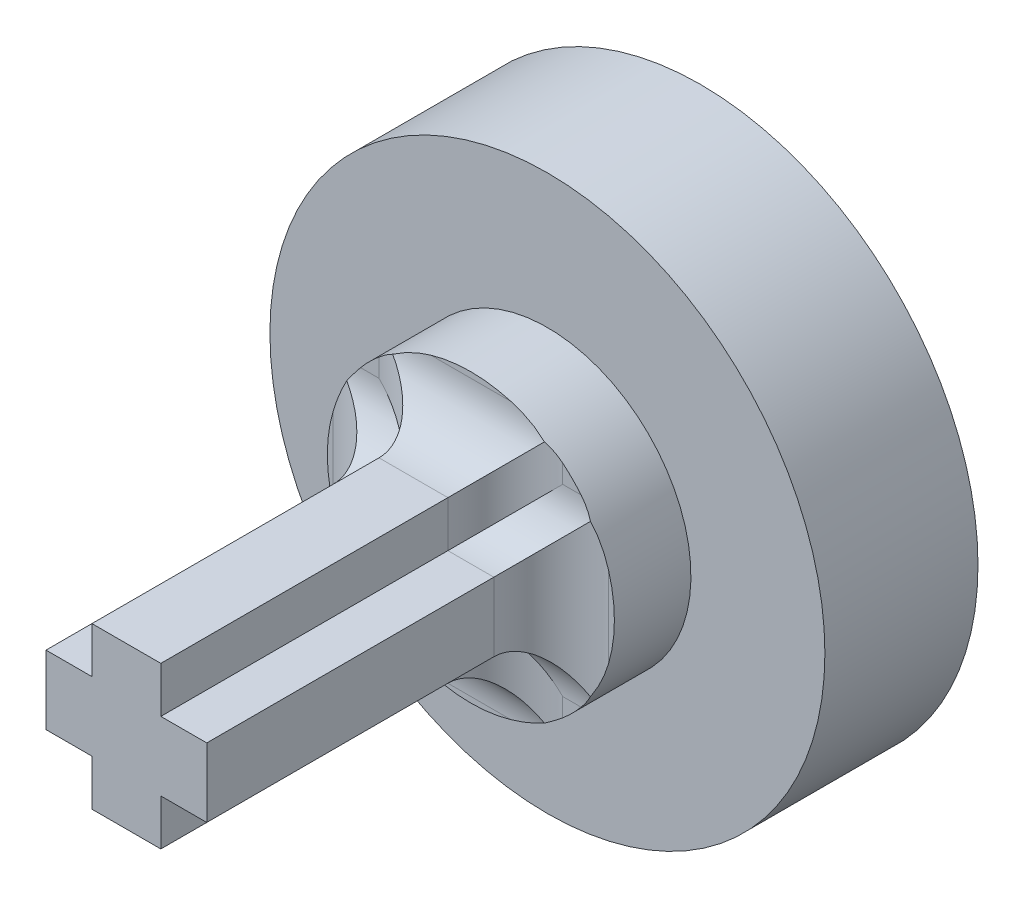
SolidWorks part; units mm, degrees
ref_plane "前视基准面" through (0, 0, 0) normal (0, 0, 1) x (1, 0, 0)
ref_plane "上视基准面" through (0, 0, 0) normal (0, 1, 0) x (1, 0, 0)
ref_plane "右视基准面" through (0, 0, 0) normal (1, 0, 0) x (0, 0, -1)
other "Configuration Table"
sketch "草图1" plane through (0, 0, 0) normal (0, 0, 1) x (1, 0, 0)
  line L1 (-0.9, -2.1) -> (0.9, -2.1)
  line L2 (-0.9, -2.1) -> (-0.9, 2.1)
  line L3 (-0.9, 2.1) -> (0.9, 2.1)
  line L4 (0.9, -2.1) -> (0.9, 2.1)
  line L5 (-0.9, -2.1) -> (0.9, 2.1) construction
  line L6 (-0.9, 2.1) -> (0.9, -2.1) construction
  line L7 (-2.1, -0.9) -> (2.1, -0.9)
  line L8 (-2.1, -0.9) -> (-2.1, 0.9)
  line L9 (-2.1, 0.9) -> (2.1, 0.9)
  line L10 (2.1, -0.9) -> (2.1, 0.9)
  line L11 (-2.1, -0.9) -> (2.1, 0.9) construction
  line L12 (-2.1, 0.9) -> (2.1, -0.9) construction
  point P0 (0, 0)
  point P6 (0, 0)
  dimension "D1" = 1.8
  dimension "D2" = 4.2
extrude "凸台-拉伸1" add sketch "草图1" along normal blind 9 contours L8 L9 L10 L7 | L3 L4 L1 L2
sketch "草图3" plane through (0, 0, 0) normal (0, 0, -1) x (-1, 0, 0)
  circle A0 centre (0, 0) radius 3.75
  dimension "D1" = 7.5
sketch "草图4" plane through (0, 0, 0) normal (0, 0, -1) x (-1, 0, 0)
  circle A0 centre (0, 0) radius 7.25
  dimension "D1" = 14.5
extrude "凸台-拉伸5" add sketch "草图3" along normal blind 2
fillet "圆角2" radius 1.5 12 edges at (0.9, -1.5, 0) (1.5, -0.9, 0) (2.1, 0, 0) (1.5, 0.9, 0) (0.9, 1.5, 0) (0, 2.1, 0) (-0.9, 1.5, 0) (-1.5, 0.9, 0) (-2.1, 0, 0) (-1.5, -0.9, 0) (-0.9, -1.5, 0) (0, -2.1, 0)
sketch "草图8" plane through (0, 0, -2) normal (0, 0, -1) x (-1, 0, 0)
  circle A0 centre (0, 0) radius 7.25
  dimension "D1" = 14.5
extrude "凸台-拉伸6" add sketch "草图8" along normal blind 4
sketch "草图7" plane through (0, 0, -6) normal (0, 0, -1) x (-1, 0, 0)
  line L0 (1.3, 1.0954) -> (1.3, -1.0954)
  circle A0 centre (0, 0) radius 1.7
  dimension "D1" = 3.4
  dimension "D2" = 1.3
extrude "切除-拉伸1" cut sketch "草图7" against normal blind 5 contours L0 A0 region at (0.1033, 0, -6)
